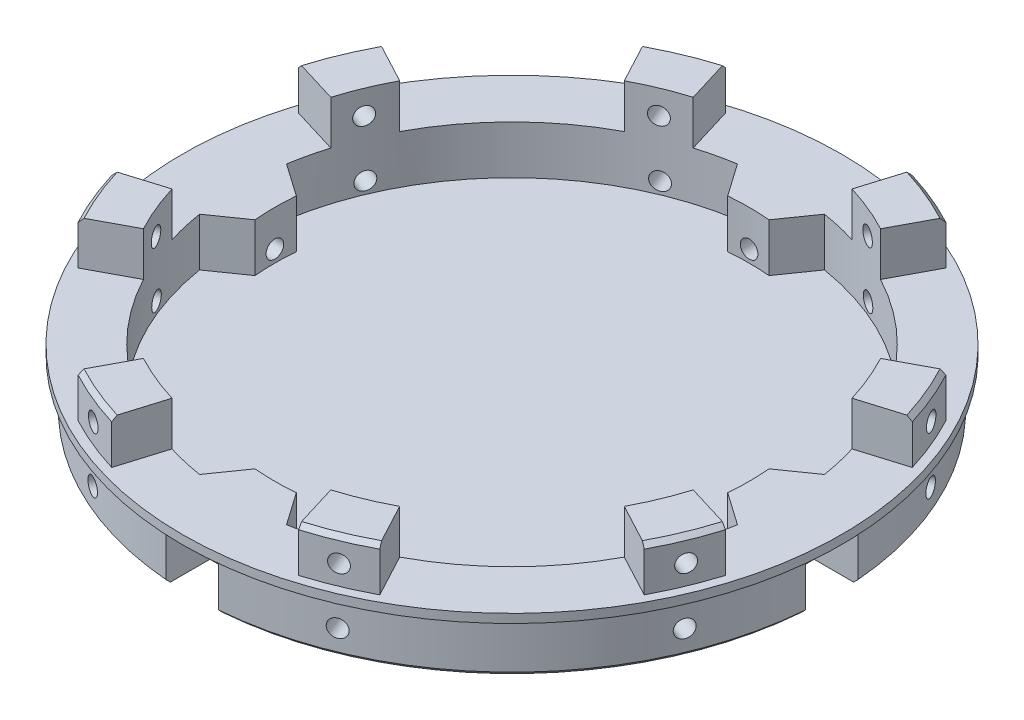
SolidWorks part; units mm, degrees
material "7075-T6, Piastra (SS)"
ref_plane "Piano frontale" through (0, 0, 0) normal (0, 0, 1) x (1, 0, 0)
ref_plane "Piano superiore" through (0, 0, 0) normal (0, 1, 0) x (1, 0, 0)
ref_plane "Piano destro" through (0, 0, 0) normal (1, 0, 0) x (0, 0, -1)
sketch "Schizzo1" plane through (0, 0, 0) normal (0, 0, 1) x (1, 0, 0)
  line L1 (-73, 24) -> (-62, 24)
  line L4 (0, 3) -> (0, 0)
  line L5 (0, 0) -> (-73, 0)
  line L7 (-73, 12) -> (-73, 0)
  line L10 (0, 0) -> (0, 105.2736) construction
  line L12 (-62, 3) -> (0, 3)
  line L13 (-73, 12) -> (-75, 12)
  line L14 (-75, 12) -> (-75, 14)
  line L15 (-75, 14) -> (-73, 14)
  line L16 (-73, 14) -> (-73, 24)
  line L19 (-62, 3) -> (-62, 0)
  line L20 (-62, 24) -> (-62, 3)
  dimension "D1" = 146
  dimension "D2" = 14
  dimension "D3" = 150
  dimension "D4" = 24
  dimension "D5" = 12
  dimension "D6" = 124
  dimension "D9" = 3
revolve "Rivoluzione1" add sketch "Schizzo1" angle 360 about L10
sketch "Schizzo2" plane through (0, 0, 0) normal (0, -1, 0) x (1, 0, 0)
  line L0 (0, 0) -> (-73, 0) construction
  line L1 (-72.753, 6) -> (-62.753, 6)
  line L2 (-62.753, 6) -> (-62.753, -6)
  line L3 (-62.753, -6) -> (-72.753, -6)
  circle A0 centre (0, 0) radius 73 construction
  arc A1 (-72.753, -6) -> (-72.753, 6) centre (0, 0) cw
  circle A2 centre (0, 0) radius 73 construction
  point P10 (-62.753, 0)
  dimension "D1" = 12
  dimension "D2" = 10
extrude "Taglio-Estrusione1" cut sketch "Schizzo2" against normal up to surface (12 mm away) up to face at (0, 12, -75)
sketch "Schizzo3" plane through (0, 24, 0) normal (0, 1, 0) x (1, 0, 0)
  line L0 (0, 0) -> (-73, 0) construction
  line L4 (0, 0) -> (-51.6188, 51.6188) construction
  line L7 (-43.8406, 43.8406) -> (-51.6188, 51.6188)
  line L8 (0, 0) -> (-67.4432, 27.9359) construction
  line L9 (0, 0) -> (-59.3078, 18.0717) construction
  line L10 (0, 0) -> (-54.7156, 29.1583) construction
  line L11 (-59.3078, 18.0717) -> (-69.8301, 21.278)
  line L12 (-54.7156, 29.1583) -> (-64.4232, 34.3315)
  line L13 (-59.3078, 18.0717) -> (-54.7156, 29.1583) construction
  line L14 (-62, 0) -> (-73, 0)
  circle A2 centre (0, 0) radius 62 construction
  arc A5 (-59.3078, 18.0717) -> (-43.8406, 43.8406) centre (0, 0) cw
  circle A6 centre (0, 0) radius 73 construction
  arc A7 (-69.8301, 21.278) -> (-51.6188, 51.6188) centre (0, 0) cw
  arc A8 (-69.8301, 21.278) -> (-64.4232, 34.3315) centre (0, 0) cw
  arc A9 (-62, 0) -> (-59.3078, 18.0717) centre (0, 0) cw
  arc A10 (-73, 0) -> (-69.8301, 21.278) centre (0, 0) cw
  point P19 (-57.0117, 23.615)
  dimension "D2" = 45
  dimension "D1" = 22.5
  dimension "D4" = 12
extrude "Taglio-Estrusione3" cut sketch "Schizzo3" against normal up to surface (10 mm away)
hole_wizard "Foro Ø4.0 (4)-1" positions "Schizzo3D1" profile "Schizzo5" hole size "Ø4.0" standard "ISO"
sketch3d "Schizzo3D1"
  point P0 (-67.4812, 18.5213, -27.8441)
sketch "Schizzo5" plane through (-67.4812, 18.5213, -27.8441) normal (0, 1, 0) x (-0.3814, 0, 0.9244)
  line L0 (0, 0) -> (0, 19)
  line L1 (0, 19) -> (2, 17.7983)
  line L2 (2, 17.7983) -> (2, 0)
  line L5 (2, 0) -> (0, 0)
  line L10 (0, 19) -> (-2, 17.7983) construction
  line L11 (0, -6.35) -> (0, 107.95) construction
  dimension "Hole Dia." = 4
  dimension "Hole Depth" = 19
  dimension "Drill Angle" = 118
hole_wizard "Foro Ø4.0 (4)-2" positions "Schizzo6" profile "Schizzo7" hole size "Ø4.0" standard "ISO"
sketch "Schizzo6" plane through (-62.753, 0, 0) normal (-1, 0, 0) x (0, 0, 1)
  point P0 (0, 5.7708)
sketch "Schizzo7" plane through (-62.753, 5.7708, 0) normal (0, 1, 0) x (0, 0, 1)
  line L0 (0, 0) -> (0, 19)
  line L1 (0, 19) -> (2, 17.7983)
  line L2 (2, 17.7983) -> (2, 0)
  line L5 (2, 0) -> (0, 0)
  line L10 (0, 19) -> (-2, 17.7983) construction
  line L11 (0, -6.35) -> (0, 107.95) construction
  dimension "Hole Dia." = 4
  dimension "Hole Depth" = 19
  dimension "Drill Angle" = 118
chamfer "Smusso1" distance 1 angle 45 1 edges at (73, 0, 0)
chamfer "Smusso2" distance 1 angle 45 1 edges at (-62.753, 0, 0)
fillet "Raccordo1" radius 1 1 edges at (-62.753, 12, 0)
chamfer "Smusso3" distance 1 angle 45 1 edges at (-67.4432, 24, -27.9359)
pattern_circular "RipetizioneCircolare5" count 8 over 360 about axis through (0, 0, 0) along (0, 1, 0) of "Foro Ø4.0 (4)-1", "Smusso3", "Taglio-Estrusione3"
pattern_circular "RipetizioneCircolare6" count 4 over 360 about axis through (0, 12, 0) along (0, -1, 0) skipping 1, 2, 3 of "Taglio-Estrusione1", "Foro Ø4.0 (4)-2", "Raccordo1", "Smusso2"
hole_wizard "Foro Ø4.0 (4)-3" positions "Schizzo3D3" profile "Schizzo9" hole size "Ø4.0" standard "ISO"
sketch3d "Schizzo3D3"
  point P0 (-67.4973, 5.7088, 27.805)
  point P2 (-67.4973, 5.7088, 27.805)
sketch "Schizzo9" plane through (-67.4973, 5.7088, 27.805) normal (0, 1, 0) x (0.3809, 0, 0.9246)
  line L0 (0, 0) -> (0, 19)
  line L1 (0, 19) -> (2, 17.7983)
  line L2 (2, 17.7983) -> (2, 0)
  line L5 (2, 0) -> (0, 0)
  line L10 (0, 19) -> (-2, 17.7983) construction
  line L11 (0, -6.35) -> (0, 107.95) construction
  dimension "Hole Dia." = 4
  dimension "Hole Depth" = 19
  dimension "Drill Angle" = 118
pattern_circular "RipetizioneCircolare7" count 8 over 360 about axis through (0, 1, 0) along (0, -1, 0) of "Foro Ø4.0 (4)-3"
sketch "Schizzo10" [suppressed] plane through (0, 3, 0) normal (0, 1, 0) x (1, 0, 0)
  circle A0 centre (0, 0) radius 62
  arc A1 (-29.1583, 54.7156) -> (-54.7156, 29.1583) centre (0, 0) ccw construction
extrude "Taglio-Estrusione4" [suppressed] cut sketch "Schizzo10" against normal blind 10
sketch "Schizzo11" plane through (0, 3, 0) normal (0, 1, 0) x (1, 0, 0)
  line L0 (-4.7064, 53.7945) -> (-5.4037, 61.7641)
  line L1 (0, 54) -> (0, 0) construction
  line L2 (4.7064, 53.7945) -> (5.4037, 61.7641)
  line L3 (-4.7064, 53.7945) -> (0, 0) construction
  line L4 (0, 0) -> (4.7064, 53.7945) construction
  arc A0 (18.0717, 59.3078) -> (-18.0717, 59.3078) centre (0, 0) ccw construction
  arc A1 (-4.7064, 53.7945) -> (4.7064, 53.7945) centre (0, 0) cw
  arc A3 (-5.4037, 61.7641) -> (5.4037, 61.7641) centre (0, 0) cw
  circle M4 centre (0, 0) radius 62
  dimension "D1" = 54
  dimension "D2" = 10
extrude "Estrusione-Estrusione1" add sketch "Schizzo11" along a picked direction on the side of the normal blind 11 contours L0 A1 L2 M4
pattern_circular "RipetizioneCircolare8" count 4 over 360 about axis through (0, 0, 0) along (0, -1, 0) of "Estrusione-Estrusione1"
sketch "Schizzo12" plane through (-62.753, 0, 0) normal (-1, 0, 0) x (0, 0, 1)
  circle A0 centre (0, 5.7708) radius 2
  circle A1 centre (0, 5.7708) radius 2 construction
extrude "Taglio-Estrusione5" cut sketch "Schizzo12" against normal blind 10
pattern_circular "RipetizioneCircolare9" count 4 over 360 about axis through (0, 0, 0) along (0, 1, 0) of "Taglio-Estrusione1", "Foro Ø4.0 (4)-2"
chamfer "Smusso5" distance 8 angle 30 2 edges at (61.7641, 8.5, 5.4037) (61.7641, 8.5, -5.4037)
chamfer "Smusso6" distance 8 angle 30 6 edges at (-5.4037, 8.5, -61.7641) (5.4037, 8.5, -61.7641) (-61.7641, 8.5, -5.4037) (-61.7641, 8.5, 5.4037) (-5.4037, 8.5, 61.7641) (5.4037, 8.5, 61.7641)
